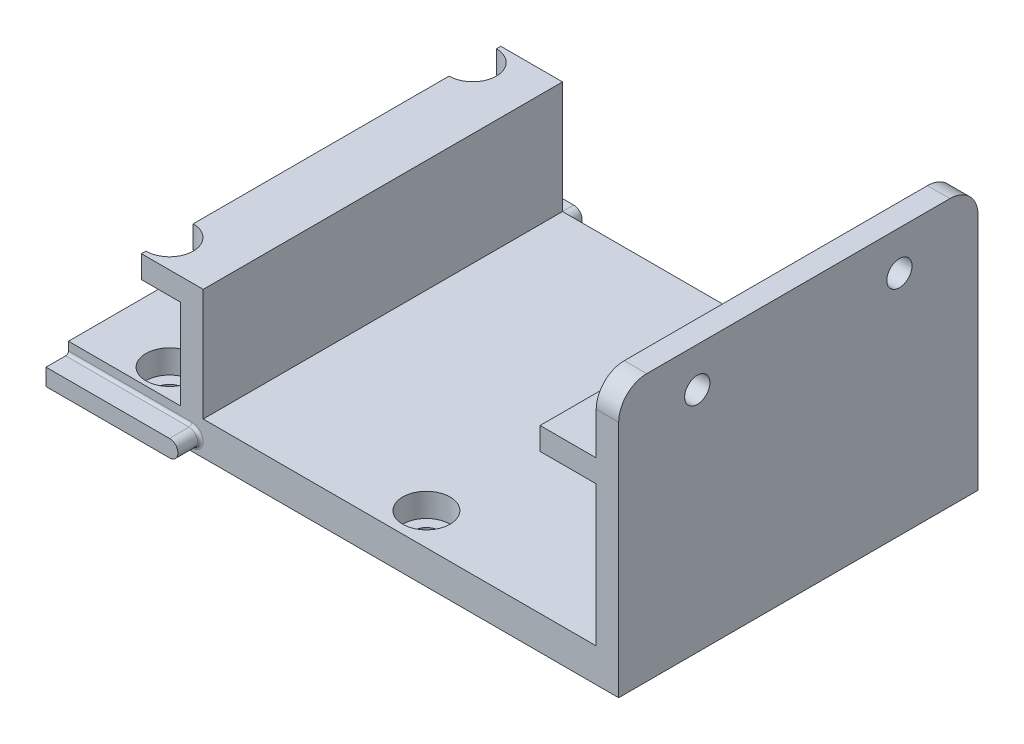
SolidWorks part; units mm, degrees
ref_plane "Front Plane" through (0, 0, 0) normal (0, 0, 1) x (1, 0, 0)
ref_plane "Top Plane" through (0, 0, 0) normal (0, 1, 0) x (1, 0, 0)
ref_plane "Right Plane" through (0, 0, 0) normal (1, 0, 0) x (0, 0, -1)
sketch "Sketch1" plane through (0, 0, 0) normal (0, 0, 1) x (1, 0, 0)
  line L0 (-14, 0) -> (0, 0)
  line L1 (0, 0) -> (0, -35)
  line L2 (0, -35) -> (-98, -35)
  line L3 (-98, -35) -> (-98, -29)
  line L4 (-98, -29) -> (-78, -29)
  line L5 (-78, -29) -> (-78, -13)
  line L6 (-78, -13) -> (-85, -13)
  line L7 (-85, -13) -> (-85, -9)
  line L8 (-85, -9) -> (-74, -9)
  line L9 (-74, -9) -> (-74, -29)
  line L10 (-74, -29) -> (-4, -29)
  line L11 (-4, -29) -> (-4, -4)
  line L12 (-4, -4) -> (-14, -4)
  line L13 (-14, -4) -> (-14, 0)
  dimension "D1" = 25
  dimension "D2" = 70
  dimension "D3" = 6
  dimension "D4" = 6
  dimension "D5" = 4
  dimension "D6" = 4
  dimension "D7" = 4
  dimension "D8" = 4
  dimension "D9" = 10
  dimension "D10" = 16
  dimension "D11" = 7
  dimension "D12" = 20
extrude "Extrude-Base" add sketch "Sketch1" along normal mid plane 64
sketch "Sketch2" plane through (0, -29, 0) normal (0, 1, 0) x (1, 0, 0)
  line L0 (0, 0) -> (-98, 0) construction
  line L1 (-98, -32) -> (-98, 32) construction
  line L2 (-4, -32) -> (-4, 32) construction
  circle A0 centre (-15, -10) radius 2.2
  circle A4 centre (-15, 10) radius 2.2
  circle A6 centre (-40, -26.25) radius 2.2479 construction
  circle A7 centre (-40, -26.25) radius 2.2479
  circle A8 centre (-40, 26.25) radius 2.2479 construction
  circle A9 centre (-40, 26.25) radius 2.2479
  circle A10 centre (-85, 27) radius 2.2 construction
  circle A11 centre (-85, 27) radius 2.2
  circle A12 centre (-85, -27) radius 2.2 construction
  circle A13 centre (-85, -27) radius 2.2
  dimension "D6" = 4.4
  dimension "D1" = 10
  dimension "D2" = 11
extrude "Cut-Bolt Holes" cut sketch "Sketch2" against normal blind 10
sketch "Sketch3" plane through (0, -29, 0) normal (0, 1, 0) x (1, 0, 0)
  line L0 (0, 0) -> (-74, 0) construction
  line L1 (-74, -32) -> (-74, 32) construction
  circle A2 centre (-15, -10) radius 4.215
  circle A3 centre (-40, 26.25) radius 4.215
  circle A4 centre (-85, -27) radius 4.215
  circle A5 centre (-15, -10) radius 2.2 construction
  circle A6 centre (-85, 27) radius 4.215
  circle A8 centre (-15, 10) radius 4.215
  circle A9 centre (-40, -26.25) radius 4.215
  circle A16 centre (-40, 26.25) radius 2.2479 construction
  dimension "D3" = 8.43
  dimension "D4" = 8.43
extrude "Cut-Bolt Head Insets" cut sketch "Sketch3" against normal blind 4.2 and the other way blind 40
sketch "Sketch4" plane through (-98, 0, 0) normal (-1, 0, 0) x (0, 0, 1)
  line L0 (32, -35) -> (-32, -35) construction
  line L1 (20, -35) -> (-20, -35)
  line L2 (20, -35) -> (20, -32)
  line L3 (20, -32) -> (-20, -32)
  line L4 (-20, -35) -> (-20, -32)
  point P7 (0, -35)
  point P8 (0, -35)
  dimension "D1" = 40
  dimension "D2" = 3
extrude "Cut-Top Clearance Slot" cut sketch "Sketch4" against normal blind 45
fillet "Fillet-Clearance Slot Pt 1" radius 3 2 edges at (-75.5, -32, 20) (-75.5, -32, -20)
fillet "Fillet-Clearance Slot Pt 2" radius 3 2 edges at (-75.5, -35, 20) (-75.5, -35, -20)
sketch "Sketch5" plane through (0, 0, 32) normal (0, 0, 1) x (1, 0, 0)
  line L0 (-78, -29) -> (-74, -29) construction
  line L1 (-76, -29) -> (-76, -35) construction
  line L2 (-98, -35) -> (0, -35) construction
  line L3 (-76, -34) -> (-98, -34)
  line L4 (-98, -29) -> (-98, -35) construction
  line L5 (-98, -34) -> (-98, -31)
  line L6 (-98, -31) -> (-76, -31)
  arc A0 (-76, -34) -> (-76, -31) centre (-76, -32.5) ccw
  point P1 (0, 0)
  point P7 (-76, -29)
  point P17 (-76, -33.5)
  point P18 (-76, -31.7507)
  dimension "D1" = 3
  dimension "D2" = 1
extrude "Boss-Extrude1" add sketch "Sketch5" along normal blind 4
sketch "Sketch7" plane through (0, 0, -32) normal (0, 0, -1) x (-1, 0, 0)
  line L0 (76, -31) -> (98, -31)
  line L1 (98, -29) -> (98, -35) construction
  line L2 (98, -31) -> (98, -34)
  line L3 (98, -34) -> (76, -34)
  circle A0 centre (76, -32.5) radius 1.5 construction
  arc A1 (76, -31) -> (76, -34) centre (76, -32.5) ccw
extrude "Boss-Extrude2" add sketch "Sketch7" along normal blind 4
sketch "Sketch9" plane through (0, 0, 0) normal (1, 0, 0) x (0, 0, -1)
  line L0 (-32, -35) -> (-32, 0) construction
  line L1 (32, 0) -> (-32, 0)
  line L2 (32, 0) -> (32, 7.5)
  line L3 (27, 12.5) -> (-27, 12.5)
  line L4 (-32, 0) -> (-32, 7.5)
  line L5 (15, 12.5) -> (-15, 12.5) construction
  line L6 (15, 12.5) -> (-15, 12.5)
  arc A0 (32, 7.5) -> (27, 12.5) centre (27, 7.5) ccw
  arc A1 (-27, 12.5) -> (-32, 7.5) centre (-27, 7.5) ccw
  circle A2 centre (-18, 5.5) radius 2.2479 construction
  circle A3 centre (-18, 5.5) radius 2.2479
  circle A4 centre (18, 5.5) radius 2.2479 construction
  circle A5 centre (18, 5.5) radius 2.2479
  dimension "D1" = 5
extrude "Boss-Extrude3" add sketch "Sketch9" against normal blind 4 contours L2 A0 L3 A1 L4 L1 | A3 | A5
fillet "Fillet1" radius 0.5 6 edges at (-87, -34, 32) (-74.5, -32.5, 32) (-87, -34, -32) (-74.5, -32.5, -32) (-87, -31, 32) (-87, -31, -32)
equation "\"holeBoltDiam\"=4.4"
equation "\"D6@Sketch2\"=\"holeBoltDiam\""
equation "\"insetBoltHead\"=8.43"
equation "\"D3@Sketch3\"=\"insetBoltHead\""
equation "\"D4@Sketch3\"=\"insetBoltHead\""
